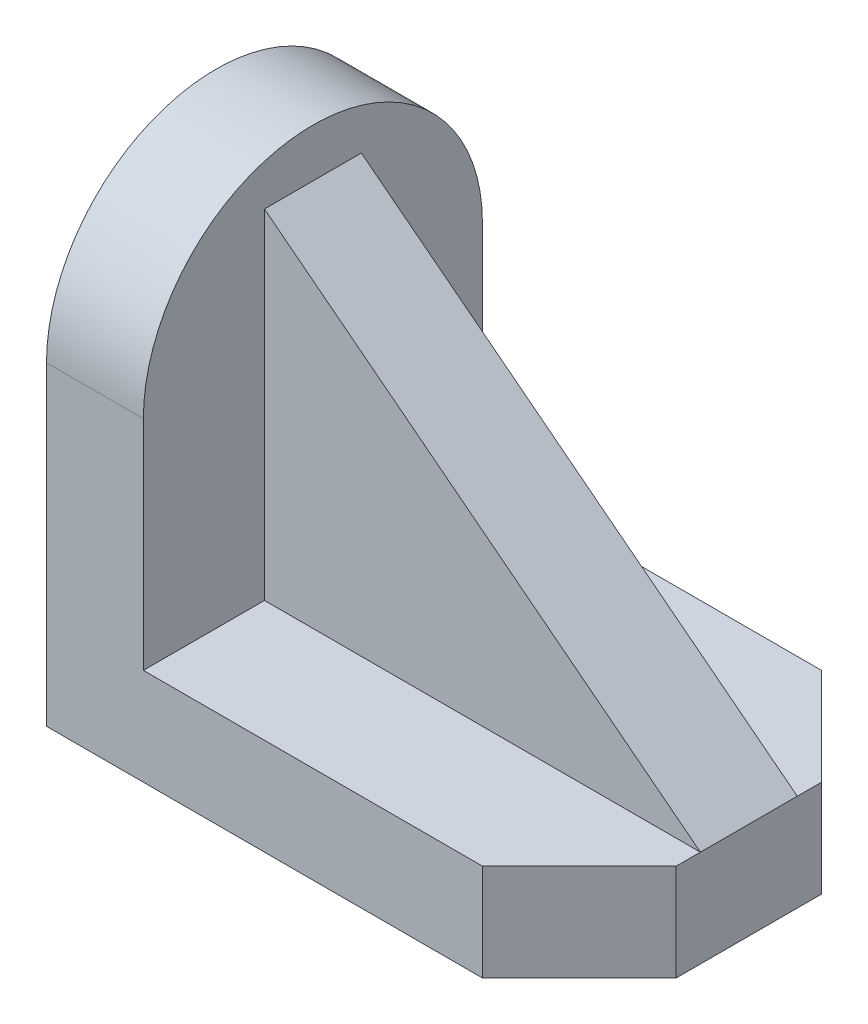
SolidWorks part; units mm, degrees
ref_plane "Front Plane" through (0, 0, 0) normal (0, 0, 1) x (1, 0, 0)
ref_plane "Top Plane" through (0, 0, 0) normal (0, 1, 0) x (1, 0, 0)
ref_plane "Right Plane" through (0, 0, 0) normal (1, 0, 0) x (0, 0, -1)
sketch "Sketch1" plane through (0, 0, 0) normal (0, 1, 0) x (1, 0, 0)
  line L1 (-48.1063, 379.5065) -> (611.8937, 379.5065)
  line L2 (-48.1063, 379.5065) -> (-48.1063, -40.4935)
  line L3 (-48.1063, -40.4935) -> (611.8937, -40.4935)
  line L4 (611.8937, 379.5065) -> (611.8937, -40.4935)
extrude "Boss-Extrude1" add sketch "Sketch1" along normal blind 120
sketch "Sketch2" plane through (0, 120, 0) normal (0, 1, 0) x (1, 0, 0)
  line L0 (-48.1063, -40.4935) -> (611.8937, -40.4935) construction
  line L1 (-48.1063, 379.5065) -> (71.8937, 379.5065)
  line L2 (-48.1063, 379.5065) -> (-48.1063, -40.4935)
  line L3 (-48.1063, -40.4935) -> (71.8937, -40.4935)
  line L4 (71.8937, 379.5065) -> (71.8937, -40.4935)
extrude "Boss-Extrude2" add sketch "Sketch2" along normal blind 480
fillet "Fillet1" 2 edges at (11.8937, 600, 40.4935) (11.8937, 600, -379.5065) type full round first side face at (211.8937, 240, 40.4935) second side face at (211.8937, 240, -379.5065) middle face at (11.8937, 600, -169.5065)
fillet "Chamfer1" radius 120 1 edges at (611.8937, 60, 40.4935) type face fillet profile chamfer first side face at (211.8937, 170, 40.4935) second side face at (611.8937, 60, -169.5065)
fillet "Chamfer2" radius 120 1 edges at (611.8937, 60, -379.5065) type face fillet profile chamfer first side face at (611.8937, 60, -229.5065) second side face at (211.8937, 170, -379.5065)
sketch "Sketch4" plane through (71.8937, 0, 0) normal (1, 0, 0) x (0, 0, -1)
  line L0 (109.5065, 120) -> (229.5065, 120)
  line L21 (79.5065, 120) -> (259.5065, 120) construction
  line L22 (109.5065, 120) -> (109.5065, 540)
  line L23 (109.5065, 540) -> (229.5065, 540)
  line L24 (229.5065, 540) -> (229.5065, 120)
  line L25 (-40.4935, 120) -> (379.5065, 120) construction
extrude "Boss-Extrude3" add sketch "Sketch4" along normal up to surface (540 mm away) up to face at (611.8937, 60, -169.5065)
sketch "Sketch7" plane through (0, 0, -109.5065) normal (0, 0, 1) x (1, 0, 0)
  line L0 (71.8937, 540) -> (611.8937, 120)
  line L1 (611.8937, 120) -> (611.8937, 540)
  line L2 (611.8937, 540) -> (71.8937, 540)
  line M5 (611.8937, 120) -> (611.8937, 540)
  line M6 (611.8937, 540) -> (71.8937, 540)
extrude "Cut-Extrude1" cut sketch "Sketch7" against normal blind 480 contours L0 M6 M5 | L2 L0 L1 region at (431.8937, 400, -109.5065)
